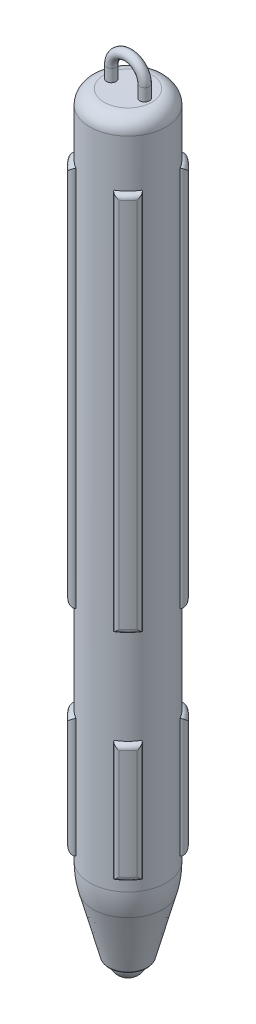
SolidWorks part; units mm, degrees
ref_plane "Alzado" through (0, 0, 0) normal (0, 0, 1) x (1, 0, 0)
ref_plane "Planta" through (0, 0, 0) normal (0, 1, 0) x (1, 0, 0)
ref_plane "Vista lateral" through (0, 0, 0) normal (1, 0, 0) x (0, 0, -1)
sketch "Croquis1" plane through (0, 0, 0) normal (0, 0, 1) x (1, 0, 0)
  line L0 (-8, 80) -> (-8, -60)
  line L4 (-4, -75) -> (0, -75)
  line L5 (0, 83) -> (0, -75)
  line L6 (-4, -75) -> (-8, -60)
  line L7 (0, 83) -> (-5, 83)
  arc A1 (-5, 83) -> (-8, 80) centre (-5, 80) ccw
  point P3 (-8, 0)
  dimension "D6" = 83
  dimension "D7" = 5
  dimension "D8" = 3
  dimension "D1" = 140
  dimension "D4" = 104.931
  dimension "D5" = 4
revolve "Revolución1" add sketch "Croquis1" angle 360 about L5
sketch "Croquis2" plane through (0, 0, 0) normal (0, 0, 1) x (1, 0, 0)
  line L0 (0, 83) -> (-3.5, 83) construction
  line L1 (5, 83) -> (-5, 83) construction
  line L2 (-3.5, 83) -> (-3.5, 85.5909)
  line L4 (0, -8.8) -> (0, 8.8) construction
  line L5 (3.5, 83) -> (3.5, 85.5909)
  arc A1 (3.5, 85.5909) -> (-3.5, 85.5909) centre (0, 85.5909) ccw
  point P14 (0, 86)
  dimension "D1" = 3.5
  dimension "D3" = 2.5909
sketch "Croquis3" plane through (0, 83, 0) normal (0, 1, 0) x (1, 0, 0)
  circle A0 centre (-3.5, 0) radius 1
  dimension "D1" = 2
sweep "Barrer5" add profiles "Croquis3" path "Croquis2"
sketch "Croquis16" plane through (0, 0, 0) normal (0, 0, 1) x (1, 0, 0)
  line L0 (-4, -75) -> (4, -75) construction
  line L1 (0, -75) -> (0, -80) construction
  line L2 (0, -78) -> (0, -72)
  arc A1 (0, -72) -> (0, -78) centre (0, -75) ccw
  dimension "D1" = 6
  dimension "D2" = 5
revolve "Revolución4" add sketch "Croquis16" angle 360 about L1
fillet "Redondeo1" radius 0.5 1 edges at (0, -75, 4)
fillet "Redondeo2" radius 20 1 edges at (0, -60, 8)
sketch "Croquis18" plane through (0, 0, 0) normal (0, 1, 0) x (1, 0, 0)
  line L0 (0, 0) -> (0, 7) construction
  line L1 (0, -8.8) -> (0, 8.8) construction
  line L2 (3.873, 7) -> (-3.873, 7)
  line L3 (-3.873, 7) -> (-3.873, 8)
  line L4 (-3.873, 8) -> (3.873, 8)
  line L5 (3.873, 7) -> (3.873, 8)
  circle A0 centre (0, 0) radius 8 construction
  point P12 (0, 8)
  dimension "D1" = 7
  dimension "D2" = 1
extrude "Cortar-Extruir1" cut sketch "Croquis18" against normal blind 150 and the other way blind 150
sketch "Croquis19" plane through (0, 0, 0) normal (0, 1, 0) x (1, 0, 0)
  line L0 (0, 0) -> (-4, 6.9282) construction
  line L1 (0, -8.8) -> (0, 8.8) construction
  line L2 (0, 0) -> (-6.9282, 4) construction
  line L3 (-8.8, 0) -> (8.8, 0) construction
  line L4 (-5.6569, 5.6569) -> (0, 0) construction
  arc A0 (-4, 6.9282) -> (-6.9282, 4) centre (0, 0) ccw
  arc A1 (-5.3236, 7.2567) -> (-7.2567, 5.3236) centre (0, 0) ccw
  arc A3 (-5.3236, 7.2567) -> (-4, 6.9282) centre (-4.7986, 6.5411) cw
  arc A4 (-7.2567, 5.3236) -> (-6.9282, 4) centre (-6.5411, 4.7986) ccw
  dimension "D4" = 18
  dimension "D5" = 0.8875
  dimension "D1" = 30
  dimension "D2" = 8
  dimension "D3" = 30
extrude "Saliente-Extruir1" add sketch "Croquis19" along normal blind 70 and the other way blind 10
pattern_circular "MatrizC1" count 4 over 360 about axis through (0, -75, 0) along (0, -1, 0) of "Saliente-Extruir1", "Revolución4"
ref_plane "Plano1" through (0, -30, 0) normal (0, -1, 0) x (-1, 0, 0)
sketch "Croquis20" plane through (0, -30, 0) normal (0, -1, 0) x (-1, 0, 0)
  arc A0 (-4, 6.9282) -> (-6.9282, 4) centre (0, 0) ccw
  arc A1 (-5.3236, 7.2567) -> (-7.2567, 5.3236) centre (0, 0) ccw
  arc A2 (-6.9282, 4) -> (-7.2567, 5.3236) centre (-6.5411, 4.7986) cw
  arc A3 (-5.3236, 7.2567) -> (-4, 6.9282) centre (-4.7986, 6.5411) cw
  dimension "D3" = 0.8875
  dimension "D4" = 0.8875
extrude "Saliente-Extruir2" add sketch "Croquis20" along normal blind 25
pattern_circular "MatrizC2" count 4 over 360 about axis through (0, -57.3791, 0) along (0, 1, 0) of "Saliente-Extruir2"
fillet "Redondeo3" radius 1 16 edges at (6.364, -55, 6.364) (-6.364, -55, 6.364) (-6.364, -30, 6.364) (-6.364, -10, -6.364) (-6.364, 70, -6.364) (-6.364, -55, -6.364) (-6.364, -30, -6.364) (6.364, -55, -6.364) (6.364, -30, -6.364) (6.364, -10, -6.364) (6.364, 70, -6.364) (6.364, -10, 6.364) (6.364, 70, 6.364) (-6.364, -10, 6.364) (-6.364, 70, 6.364) (6.364, -30, 6.364)
ref_plane "Plano2" through (0, -20, 0) normal (0, 1, 0) x (1, 0, 0)
sketch "Croquis22" plane through (0, -20, 0) normal (0, 1, 0) x (1, 0, 0)
  line L0 (0, -8) -> (0, -34.9933) construction
  line L1 (2, -9) -> (-2, -9) construction
  line L2 (-2, -9.161) -> (-2, -7.746)
  line L3 (-2, -7.746) -> (2, -7.746)
  line L4 (0, -23.6463) -> (0, 23.6463) construction
  line L5 (2, -9.161) -> (2, -7.746)
  line L6 (0.08, -21.9936) -> (0, -22.1321)
  line L8 (-5.42, -31.5198) -> (-6.42, -33.2519)
  line L9 (5.5396, -31.4498) -> (6.5396, -33.182)
  arc A1 (-2, -9.161) -> (-6.42, -33.2519) centre (0.08, -21.9936) ccw
  arc A2 (0, -10.9938) -> (-5.42, -31.5198) centre (0.08, -21.9936) ccw
  arc A3 (0, -10.9938) -> (5.5396, -31.4498) centre (-0.08, -21.9936) cw
  arc A4 (2, -9.161) -> (6.5396, -33.182) centre (-0.08, -21.9936) cw
  point P17 (0, -9)
  point P20 (0, -7.746)
  dimension "D4" = 8
  dimension "D1" = 13
  dimension "D7" = 22
  dimension "D2" = 2
  dimension "D3" = 1
  dimension "D5" = 1.4151
  dimension "D6" = 2
  dimension "D8" = 14.2476
  dimension "D9" = 30
  dimension "D10" = 2.0001
